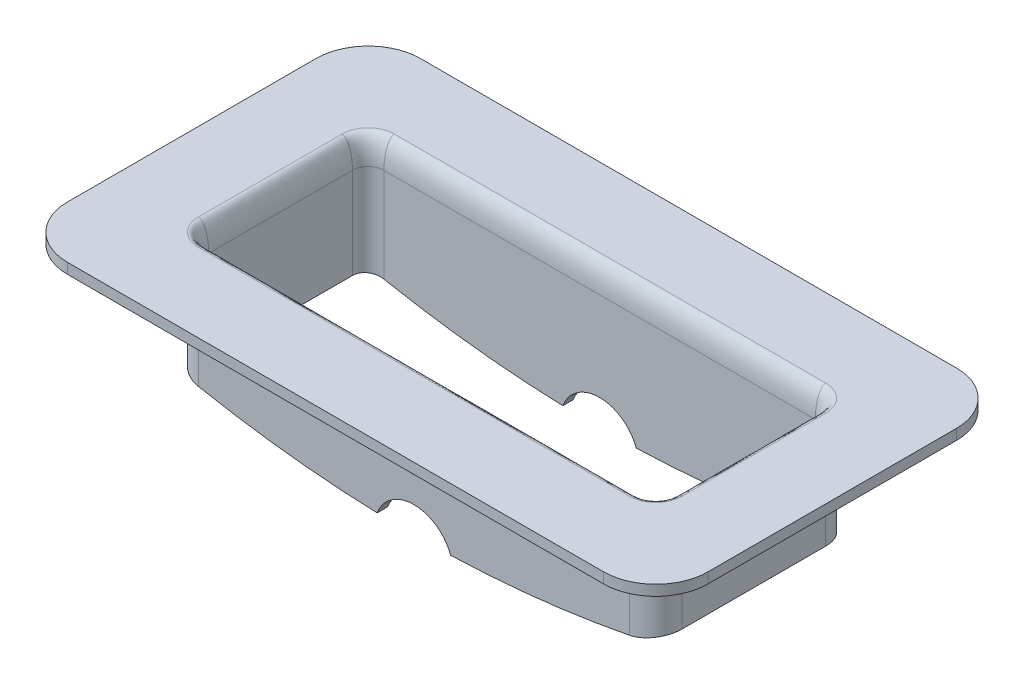
SolidWorks part; units mm, degrees
ref_plane "Front Plane" through (0, 0, 0) normal (0, 0, 1) x (1, 0, 0)
ref_plane "Top Plane" through (0, 0, 0) normal (0, 1, 0) x (1, 0, 0)
ref_plane "Right Plane" through (0, 0, 0) normal (1, 0, 0) x (0, 0, -1)
sketch "Sketch1" plane through (0, 0, 0) normal (0, 1, 0) x (1, 0, 0)
  line L0 (-56.1975, 17.4625) -> (-56.1975, -17.4625)
  line L1 (-52.3875, 23.8125) -> (52.3875, 23.8125)
  line L2 (-58.7375, 17.4625) -> (-58.7375, -17.4625)
  line L3 (-52.3875, -23.8125) -> (52.3875, -23.8125)
  line L4 (58.7375, 17.4625) -> (58.7375, -17.4625)
  line L5 (-58.7375, 23.8125) -> (58.7375, -23.8125) construction
  line L6 (-58.7375, -23.8125) -> (58.7375, 23.8125) construction
  line L7 (-52.3875, -21.2725) -> (52.3875, -21.2725)
  line L8 (56.1975, 17.4625) -> (56.1975, -17.4625)
  line L9 (-52.3875, 21.2725) -> (52.3875, 21.2725)
  arc A0 (52.3875, 23.8125) -> (58.7375, 17.4625) centre (52.3875, 17.4625) cw
  arc A1 (52.3875, -23.8125) -> (58.7375, -17.4625) centre (52.3875, -17.4625) ccw
  arc A2 (-58.7375, -17.4625) -> (-52.3875, -23.8125) centre (-52.3875, -17.4625) ccw
  arc A3 (-52.3875, 23.8125) -> (-58.7375, 17.4625) centre (-52.3875, 17.4625) ccw
  arc A4 (-56.1975, -17.4625) -> (-52.3875, -21.2725) centre (-52.3875, -17.4625) ccw
  arc A5 (52.3875, -21.2725) -> (56.1975, -17.4625) centre (52.3875, -17.4625) ccw
  arc A6 (52.3875, 21.2725) -> (56.1975, 17.4625) centre (52.3875, 17.4625) cw
  arc A7 (-52.3875, 21.2725) -> (-56.1975, 17.4625) centre (-52.3875, 17.4625) ccw
  point P0 (0, 0)
  dimension "D1" = 6.35
  dimension "D2" = 117.475
  dimension "D3" = 47.625
  dimension "D4" = 2.54
extrude "Boss-Extrude1" add sketch "Sketch1" along normal blind 31.75
sketch "Sketch2" plane through (0, 31.75, 0) normal (0, 1, 0) x (1, 0, 0)
  line L0 (52.3875, 23.8125) -> (-52.3875, 23.8125) construction
  line L1 (-65.0875, -42.8625) -> (65.0875, -42.8625)
  line L2 (-77.7875, -30.1625) -> (-77.7875, 30.1625)
  line L3 (-65.0875, 42.8625) -> (65.0875, 42.8625)
  line L4 (77.7875, -30.1625) -> (77.7875, 30.1625)
  line L5 (-77.7875, -42.8625) -> (77.7875, 42.8625) construction
  line L6 (-77.7875, 42.8625) -> (77.7875, -42.8625) construction
  line L7 (-58.7375, 17.4625) -> (-58.7375, -17.4625) construction
  line L12 (-56.1975, 17.4625) -> (-56.1975, -17.4625) construction
  line L13 (-52.3875, -21.2725) -> (52.3875, -21.2725) construction
  line L14 (56.1975, -17.4625) -> (56.1975, 17.4625) construction
  line L15 (52.3875, 21.2725) -> (-52.3875, 21.2725) construction
  line L16 (52.3875, 21.2725) -> (-52.3875, 21.2725)
  line L17 (56.1975, -17.4625) -> (56.1975, 17.4625)
  line L18 (-52.3875, -21.2725) -> (52.3875, -21.2725)
  line L19 (-56.1975, 17.4625) -> (-56.1975, -17.4625)
  arc A0 (65.0875, 42.8625) -> (77.7875, 30.1625) centre (65.0875, 30.1625) cw
  arc A1 (65.0875, -42.8625) -> (77.7875, -30.1625) centre (65.0875, -30.1625) ccw
  arc A2 (-65.0875, -42.8625) -> (-77.7875, -30.1625) centre (-65.0875, -30.1625) cw
  arc A3 (-77.7875, 30.1625) -> (-65.0875, 42.8625) centre (-65.0875, 30.1625) cw
  arc A12 (52.3875, -21.2725) -> (56.1975, -17.4625) centre (52.3875, -17.4625) ccw construction
  arc A13 (56.1975, 17.4625) -> (52.3875, 21.2725) centre (52.3875, 17.4625) ccw construction
  arc A14 (-52.3875, 21.2725) -> (-56.1975, 17.4625) centre (-52.3875, 17.4625) ccw construction
  arc A15 (-52.3875, 21.2725) -> (-56.1975, 17.4625) centre (-52.3875, 17.4625) ccw
  arc A20 (56.1975, 17.4625) -> (52.3875, 21.2725) centre (52.3875, 17.4625) ccw
  arc A21 (52.3875, -21.2725) -> (56.1975, -17.4625) centre (52.3875, -17.4625) ccw
  arc A22 (-56.1975, -17.4625) -> (-52.3875, -21.2725) centre (-52.3875, -17.4625) ccw construction
  arc A23 (-56.1975, -17.4625) -> (-52.3875, -21.2725) centre (-52.3875, -17.4625) ccw
  point P0 (0, 0)
  dimension "D3" = 12.7
  dimension "D1" = 19.05
  dimension "D2" = 19.05
extrude "Boss-Extrude2" add sketch "Sketch2" along normal blind 2.54
fillet "Fillet1" radius 5.715 8 edges at (-56.8776, 31.75, -21.9526) (0, 31.75, -23.8125) (56.8776, 31.75, -21.9526) (58.7375, 31.75, 0) (56.8776, 31.75, 21.9526) (0, 31.75, 23.8125) (-56.8776, 31.75, 21.9526) (-58.7375, 31.75, 0)
fillet "Fillet3" radius 2.54 8 edges at (0, 34.29, 21.2725) (55.0816, 34.29, 20.1566) (-55.0816, 34.29, 20.1566) (56.1975, 34.29, 0) (-56.1975, 34.29, 0) (55.0816, 34.29, -20.1566) (-55.0816, 34.29, -20.1566) (0, 34.29, -21.2725) second distance 6.35 first distance on face at (0, 34.29, 0)
sketch "Sketch3" plane through (0, 0, 23.8125) normal (0, 0, 1) x (1, 0, 0)
  line L0 (-65.0875, 31.75) -> (65.0875, 31.75) construction
  line L1 (-52.3875, 0) -> (52.3875, 0) construction
  line L2 (-58.7375, 26.035) -> (-58.7375, 0) construction
  line L3 (58.7375, 26.035) -> (58.7375, 0) construction
  line L4 (52.3875, 0) -> (58.7375, 0) construction
  line L5 (-58.7375, 0) -> (-52.3875, 0) construction
  line L6 (58.7375, 6.35) -> (58.7375, 0)
  line L7 (52.3875, 0) -> (58.7375, 0)
  line L8 (-58.7375, 6.35) -> (-58.7375, 0)
  line L9 (-58.7375, 0) -> (-52.3875, 0)
  line L10 (-52.3875, 0) -> (52.3875, 0)
  circle A0 centre (0, -3.175) radius 9.525
  arc A1 (-58.7375, 6.35) -> (58.7375, 6.35) centre (0, 274.8359) ccw
  point P2 (0, 31.75)
  point P4 (0, 6.35)
  point P11 (-58.7375, 6.35)
  point P12 (-58.7375, 14.4133)
  point P15 (0, 0)
  point P16 (-58.7375, 6.35)
  line M2 (52.3875, 0) -> (52.3875, 26.035)
  line M4 (-52.3875, 26.035) -> (-52.3875, 0)
  line M5 (-52.3875, 0) -> (52.3875, 0)
  dimension "D2" = 19.05
  dimension "D1" = 25.4
  dimension "D3" = 25.4
extrude "Cut-Extrude1" cut sketch "Sketch3" against normal through all contours A1 L8 L9 M4 | A1 A0 M4 M5 | A0 A1 | A1 A0 L10 | A1 A0 M5 | A1 A0 M5 M2 | A1 L7 L6 M2 region at (55.6846, 2.8534, 23.8125) region at (39.4775, 1.5166, 23.8125) region at (0, 2.6576, 23.8125) region at (6.7157, 0.0436, 23.8125) region at (-6.7157, 0.0436, 23.8125) region at (-39.4775, 1.5166, 23.8125) region at (-55.6846, 2.8534, 23.8125)
